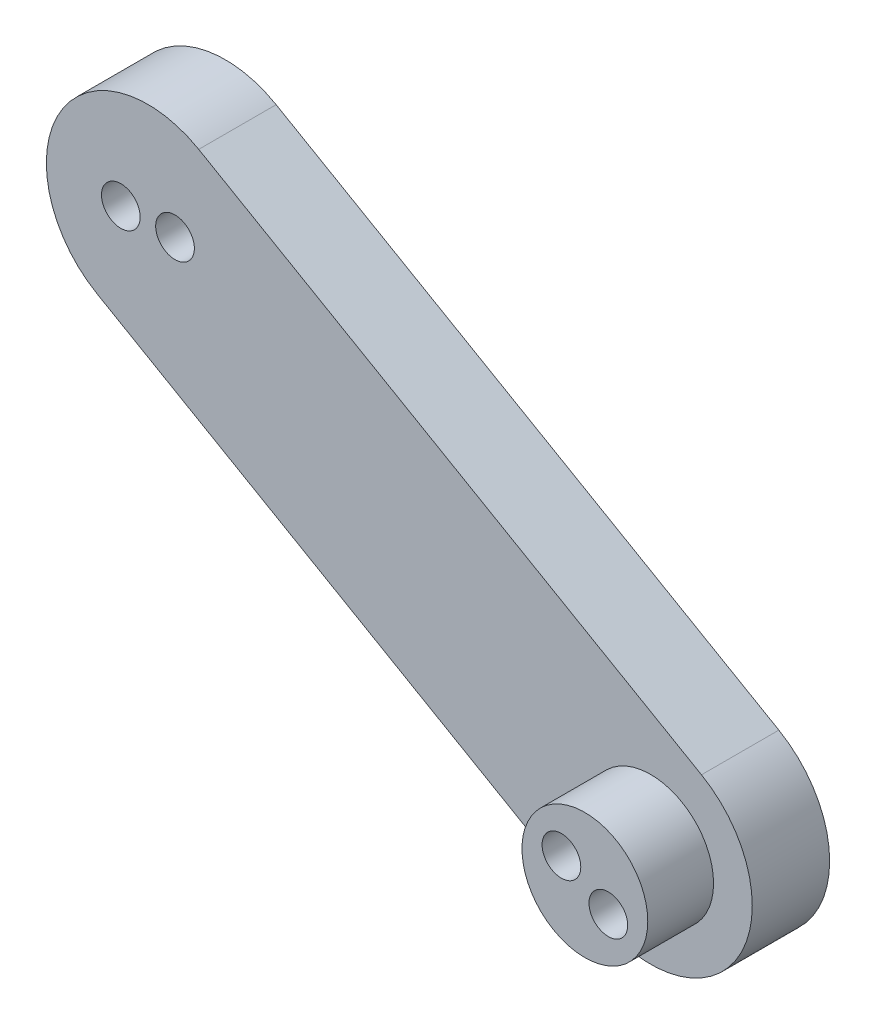
SolidWorks part; units mm, degrees
material "ABS"
ref_plane "Front Plane" through (0, 0, 0) normal (0, 0, 1) x (1, 0, 0)
ref_plane "Top Plane" through (0, 0, 0) normal (0, 1, 0) x (1, 0, 0)
ref_plane "Right Plane" through (0, 0, 0) normal (1, 0, 0) x (0, 0, -1)
sketch "Link Sketch" plane through (0, 0, 0) normal (0, 0, 1) x (1, 0, 0)
  line L0 (0, 0) -> (1.4, 0) construction
  line L1 (23.3558, -19.5466) -> (-2.625, -4.5466)
  line L2 (2.625, 4.5466) -> (28.6058, -10.4534)
  line L3 (25.9808, -15) -> (24.7683, -14.3) construction
  line L4 (27.1932, -15.7) -> (25.9808, -15) construction
  line L5 (24.7683, -14.3) -> (0, 0) construction
  line L6 (0, 0) -> (-1.4, 0) construction
  circle A0 centre (-1.4, 0) radius 1
  circle A1 centre (1.4, 0) radius 1
  arc A2 (2.625, 4.5466) -> (-2.625, -4.5466) centre (0, 0) ccw
  arc A3 (23.3558, -19.5466) -> (28.6058, -10.4534) centre (25.9808, -15) ccw
  circle A4 centre (24.7683, -14.3) radius 1
  circle A5 centre (27.1932, -15.7) radius 1
  circle A6 centre (25.9808, -15) radius 3.25
  dimension "Hole Diameter" = 2
  dimension "Output Link Distance" = 30
  dimension "Hole Pair Gap" = 0.8
  dimension "Hole Edge to Joint" = 0.85
  dimension "Joint OD to Flange" = 2
  dimension "Link Angle" = 30
extrude "Link Extrude" add sketch "Link Sketch" against normal blind 4 contours L1 A3 L2 A2 A6 A0 A1 | A6 A4 A5 region at (12.0254, -6.9429, 0) region at (25.9808, -15, 0)
extrude "Joint Extrude" add sketch "Sketch1<3>" along normal blind 3.4 contours A6 A4 A5 region at (25.9808, -15, 0)
sketch "Sketch1<3>" plane through (0, 0, 0) normal (0, 0, 1) x (1, 0, 0) same geometry as "Link Sketch"
